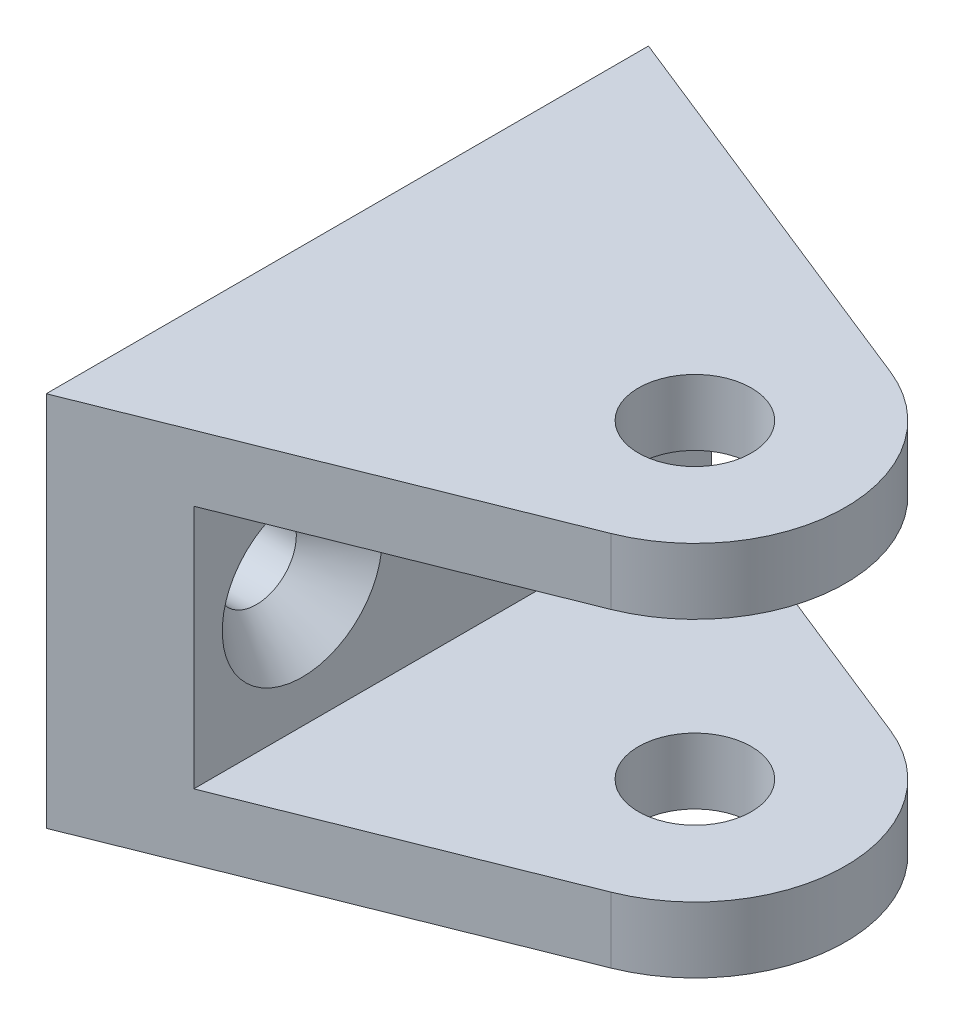
SolidWorks part; units mm, degrees
ref_plane "Front Plane" through (0, 0, 0) normal (0, 0, 1) x (1, 0, 0)
ref_plane "Top Plane" through (0, 0, 0) normal (0, 1, 0) x (1, 0, 0)
ref_plane "Right Plane" through (0, 0, 0) normal (1, 0, 0) x (0, 0, -1)
sketch "Sketch1" plane through (0, 0, 0) normal (0, 0, 1) x (1, 0, 0)
  line L0 (0, 0) -> (42.0157, 0)
  line L1 (42.0157, 0) -> (42.0157, 5.5499)
  line L2 (42.0157, 5.5499) -> (8.89, 5.5499)
  line L3 (8.89, 5.5499) -> (8.89, 26.2001)
  line L4 (8.89, 26.2001) -> (42.0157, 26.2001)
  line L5 (42.0157, 26.2001) -> (42.0157, 31.75)
  line L6 (42.0157, 31.75) -> (0, 31.75)
  line L7 (0, 31.75) -> (0, 0)
  line L8 (29.3157, 31.75) -> (29.3157, 0) construction
  dimension "D1" = 31.75
  dimension "D2" = 20.6502
  dimension "D3" = 12.7
  dimension "D4" = 8.89
extrude "Boss-Extrude1" add sketch "Sketch1" along normal blind 50.8
sketch "Sketch2" plane through (8.89, 0, 0) normal (1, 0, 0) x (0, 0, -1)
  line L0 (-25.4, 31.75) -> (-25.4, 0) construction
  line L1 (-50.8, 31.75) -> (0, 31.75) construction
  line L2 (-50.8, 0) -> (0, 0) construction
  line L3 (-38.1, 15.875) -> (-12.7, 15.875) construction
  circle A0 centre (-38.1, 15.875) radius 3.175
  circle A1 centre (-12.7, 15.875) radius 3.175
  point P6 (-38.1, 15.875)
  point P7 (-12.7, 15.875)
  point P8 (-25.4, 15.875)
  point P15 (-12.7, 15.875)
  point P17 (-38.1, 15.875)
  dimension "D2" = 6.35
  dimension "D1" = 25.4
hole_wizard "CSK for 1/4 Flat Head Machine Screw (100)1" positions "Sketch2" profile "Sketch7" countersink size "1/4" standard "ANSI Inch" end condition through all
sketch "Sketch7" plane through (8.89, 15.875, 38.1) normal (0, 1, 0) x (0, 0, -1)
  line L0 (0, 0) -> (0, 8.89)
  line L1 (0, 8.89) -> (3.3782, 8.89)
  line L2 (3.3782, 8.89) -> (3.3782, 3.8716)
  line L3 (3.3782, 3.8716) -> (6.7437, 0)
  line L5 (6.7437, 0) -> (0, 0)
  line L6 (-3.3782, 3.8716) -> (-6.7437, 0) construction
  line L11 (0, -6.35) -> (0, 107.95) construction
  dimension "Thru Hole Dia." = 6.7564
  dimension "Thru Hole Depth" = 8.89
  dimension "Near C'Sink Dia." = 13.4874
  dimension "Near C'Sink Angle" = 82
sketch "Sketch3" plane through (0, 0, 0) normal (0, -1, 0) x (1, 0, 0)
  line L0 (34701.1242, 25.4) -> (-34766.6696, 25.4) construction
  circle A0 centre (29.3157, 25.4) radius 4.7625
  dimension "D1" = 9.525
extrude "Spherical Holes " cut sketch "Sketch3" against normal up to surface (31.75 mm away) up to face at (21.0078, 31.75, 25.4)
sketch "Sketch4" plane through (0, 31.75, 0) normal (0, 1, 0) x (1, 0, 0)
  line L0 (42.0157, -50.8) -> (42.0157, 0) construction
  line L1 (0, 0) -> (34.031, -13.6078)
  line L2 (0, -50.8) -> (34.031, -37.1922)
  line L5 (0, 0) -> (0, -50.8)
  arc A0 (34.031, -37.1922) -> (34.031, -13.6078) centre (29.3157, -25.4) ccw
extrude "Rounding" cut sketch "Sketch4" against normal up to surface (31.75 mm away) flip side to cut up to face at (29.3157, 0, 20.6375)
